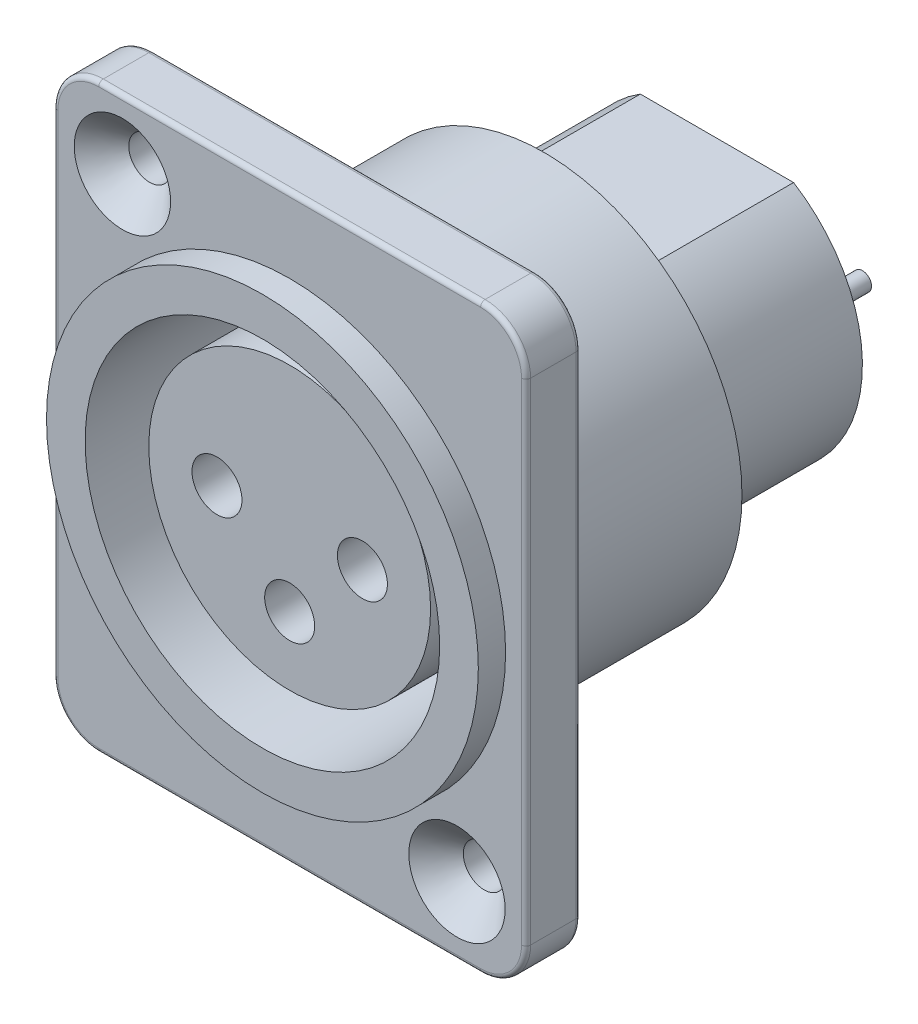
SolidWorks part; units mm, degrees
ref_plane "Alzado" through (0, 0, 0) normal (0, 0, 1) x (1, 0, 0)
ref_plane "Planta" through (0, 0, 0) normal (0, 1, 0) x (1, 0, 0)
ref_plane "Vista lateral" through (0, 0, 0) normal (1, 0, 0) x (0, 0, -1)
sketch "Croquis1" plane through (0, 0, 0) normal (0, 0, 1) x (1, 0, 0)
  line L0 (-4.2143, 6.8) -> (4.2143, 6.8)
  arc A0 (-4.2143, 6.8) -> (4.2143, 6.8) centre (0, 0) ccw
  dimension "D1" = 8
  dimension "D2" = 6.8
extrude "Saliente-Extruir1" add sketch "Croquis1" along normal blind 9.5
sketch "Croquis2" plane through (0, 0, 9.5) normal (0, 0, 1) x (1, 0, 0)
  circle A0 centre (0, 0) radius 10.875
  dimension "D1" = 21.75
extrude "Saliente-Extruir2" add sketch "Croquis2" along normal blind 11
sketch "Croquis3" plane through (0, 0, 20.5) normal (0, 0, 1) x (1, 0, 0)
  line L1 (13, -16) -> (-13, -16)
  line L2 (13, -16) -> (13, 16)
  line L3 (13, 16) -> (-13, 16)
  line L4 (-13, -16) -> (-13, 16)
  line L5 (13, -16) -> (-13, 16) construction
  line L6 (13, 16) -> (-13, -16) construction
  point P0 (0, 0)
  dimension "D1" = 26
  dimension "D2" = 32
extrude "Saliente-Extruir3" add sketch "Croquis3" along normal blind 3
fillet "Redondeo1" radius 2.5 4 edges at (13, -16, 22) (-13, -16, 22) (-13, 16, 22) (13, 16, 22)
sketch "Croquis4" plane through (0, 0, 23.5) normal (0, 0, 1) x (1, 0, 0)
  line L0 (-4, 0) -> (0, 0) construction
  line L1 (0, 0) -> (4, 0) construction
  line L2 (0, 0) -> (0, -4) construction
  circle A0 centre (0, 0) radius 9.75
  circle A1 centre (0, 0) radius 7.75
  circle A2 centre (0, 0) radius 11.875
  circle A3 centre (-4, 0) radius 1.375
  circle A4 centre (0, -4) radius 1.375
  circle A5 centre (4, 0) radius 1.375
  dimension "D1" = 19.5
  dimension "D2" = 23.75
  dimension "D3" = 15.5
  dimension "D4" = 2.75
  dimension "D5" = 4
extrude "Saliente-Extruir4" add sketch "Croquis4" along normal blind 1.5 contours A2 A0 region at (-11.5391, 0, 23.5)
extrude "Cortar-Extruir1" cut sketch "Croquis4<3>" against normal blind 10 contours A3 | A4 | A5 | A0 A1 region at (-9.4742, 0, 23.5) region at (-4, 0, 23.5) region at (0, -4, 23.5) region at (4, 0, 23.5)
sketch "Croquis4<3>" plane through (0, 0, 23.5) normal (0, 0, 1) x (1, 0, 0) same geometry as "Croquis4"
sketch "Croquis5" plane through (0, 0, 23.5) normal (0, 0, 1) x (1, 0, 0)
  line L0 (-9.2, 12.25) -> (9.2, -12.25) construction
  line L1 (9.2, -12.25) -> (9.2, -13.4) construction
  line L2 (-9.2, 13.4) -> (-9.2, 16) construction
  line L3 (-10.5, -16) -> (10.5, -16) construction
  line L4 (10.5, 16) -> (-10.5, 16) construction
  line L5 (10.35, -12.25) -> (13, -12.25) construction
  line L6 (13, -13.5) -> (13, 13.5) construction
  circle A0 centre (-9.2, 12.25) radius 1.15
  circle A1 centre (9.2, -12.25) radius 1.15
  dimension "D2" = 2.3
  dimension "D1" = 2.6
  dimension "D3" = 2.65
extrude "Cortar-Extruir2" cut sketch "Croquis5" against normal up to next
chamfer "Chaflán1" distance 1.5 angle 45 2 edges at (10.35, -12.25, 23.5) (-8.05, 12.25, 23.5)
sketch "Croquis6" plane through (0, 0, 0) normal (0, 0, -1) x (-1, 0, 0)
  circle A0 centre (-4, 0) radius 1.375 construction
  circle A1 centre (4, 0) radius 1.375 construction
  circle A2 centre (0, -4) radius 1.375 construction
  circle A3 centre (-4, 0) radius 1.375
  circle A4 centre (4, 0) radius 1.375
  circle A5 centre (0, -4) radius 1.375
  circle A6 centre (-4, 0) radius 0.5
  circle A7 centre (0, -4) radius 0.5
  circle A8 centre (4, 0) radius 0.5
  dimension "D1" = 1
extrude "Saliente-Extruir5" add sketch "Croquis6" along normal blind 1 contours A6 | A3 A6 | A8 | A4 A8 | A5 A7 | A7 region at (5.3361, 0, 0) region at (-2.6639, 0, 0) region at (1.3361, -4, 0) region at (4, 0, 0) region at (0, -4, 0) region at (-4, 0, 0)
extrude "Saliente-Extruir6" add sketch "Croquis6<3>" along normal blind 4 contours A6 | A8 | A7
sketch "Croquis6<3>" plane through (0, 0, 0) normal (0, 0, -1) x (-1, 0, 0) same geometry as "Croquis6"
fillet "Redondeo2" radius 0.25 16 edges at (12.2678, 15.2678, 20.5) (13, 0, 20.5) (12.2678, -15.2678, 20.5) (0, -16, 20.5) (-12.2678, -15.2678, 20.5) (-13, 0, 20.5) (-12.2678, 15.2678, 20.5) (12.2678, 15.2678, 23.5) (13, 0, 23.5) (12.2678, -15.2678, 23.5) (0, -16, 23.5) (-12.2678, -15.2678, 23.5) (-13, 0, 23.5) (-12.2678, 15.2678, 23.5) (0, 16, 20.5) (0, 16, 23.5)
